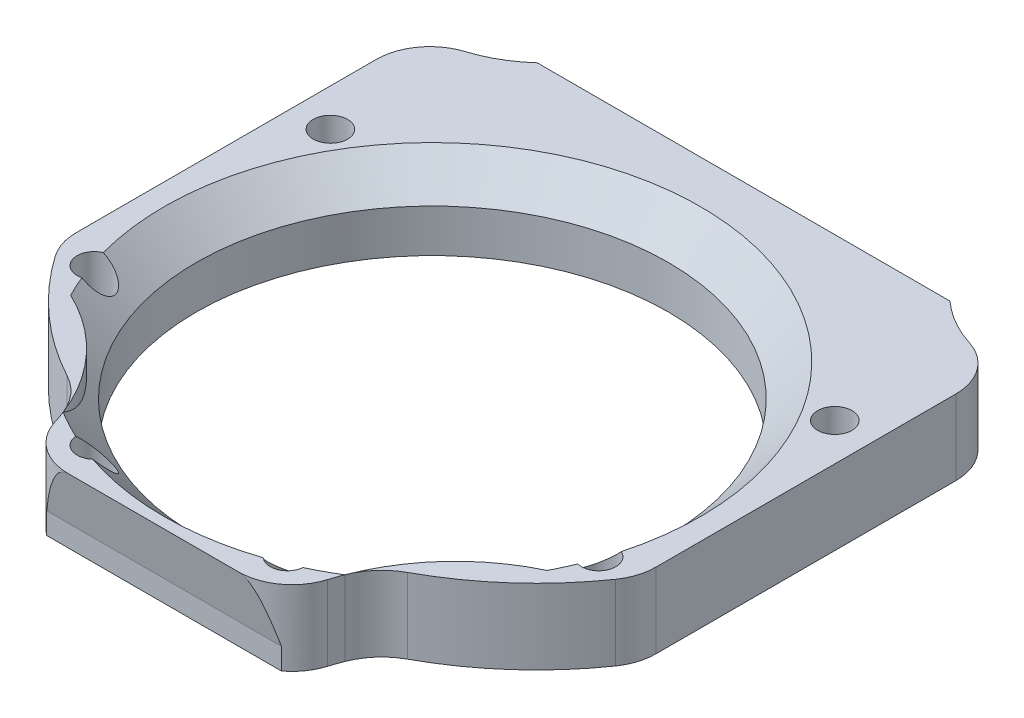
SolidWorks part; units mm, degrees
material "PBT Общее назначение"
ref_plane "Спереди" through (0, 0, 0) normal (0, 0, 1) x (1, 0, 0)
ref_plane "Сверху" through (0, 0, 0) normal (0, 1, 0) x (1, 0, 0)
ref_plane "Справа" through (0, 0, 0) normal (1, 0, 0) x (0, 0, -1)
ref_plane "Плоскость4" through (0, -5, 0) normal (0, -1, 0) x (-1, 0, 0)
sketch "Эскиз2" plane through (0, -5, 0) normal (0, -1, 0) x (-1, 0, 0)
  line L4 (-23.9302, -60) -> (-8.0698, -60)
  line L5 (-43, -12.2273) -> (-43, -40.1669)
  line L6 (3.2299, -5) -> (-35.2299, -5)
  line L7 (11, -40.1669) -> (11, -12.2273)
  line L8 (-23.9302, -60) -> (-8.0698, -60)
  line L9 (-43, -12.2273) -> (-43, -40.1669)
  line L10 (3.2299, -5) -> (-35.2299, -5)
  line L11 (11, -40.1669) -> (11, -12.2273)
  arc A10 (7.7203, -44.8616) -> (11, -40.1669) centre (6, -40.1669) ccw
  arc A11 (7.7203, -44.8616) -> (-3.2909, -56.4701) centre (13.9135, -61.7626) ccw
  arc A12 (-8.0698, -60) -> (-3.2909, -56.4701) centre (-8.0698, -55) ccw
  arc A13 (-28.7091, -56.4701) -> (-23.9302, -60) centre (-23.9302, -55) ccw
  arc A14 (-28.7091, -56.4701) -> (-39.7203, -44.8616) centre (-45.9135, -61.7626) ccw
  arc A15 (-43, -40.1669) -> (-39.7203, -44.8616) centre (-38, -40.1669) ccw
  arc A16 (-39.5094, -7.4605) -> (-43, -12.2273) centre (-38, -12.2273) ccw
  arc A17 (-39.5094, -7.4605) -> (-35.2299, -5) centre (-43, 3.5625) ccw
  arc A18 (3.2299, -5) -> (7.5094, -7.4605) centre (11, 3.5625) ccw
  arc A19 (11, -12.2273) -> (7.5094, -7.4605) centre (6, -12.2273) ccw
  arc A20 (7.7203, -44.8616) -> (11, -40.1669) centre (6, -40.1669) ccw
  arc A21 (7.7203, -44.8616) -> (-3.2909, -56.4701) centre (13.9135, -61.7626) ccw
  arc A22 (-8.0698, -60) -> (-3.2909, -56.4701) centre (-8.0698, -55) ccw
  arc A23 (-28.7091, -56.4701) -> (-23.9302, -60) centre (-23.9302, -55) ccw
  arc A24 (-28.7091, -56.4701) -> (-39.7203, -44.8616) centre (-45.9135, -61.7626) ccw
  arc A25 (-43, -40.1669) -> (-39.7203, -44.8616) centre (-38, -40.1669) ccw
  arc A26 (-39.5094, -7.4605) -> (-43, -12.2273) centre (-38, -12.2273) ccw
  arc A27 (-39.5094, -7.4605) -> (-35.2299, -5) centre (-43, 3.5625) ccw
  arc A28 (3.2299, -5) -> (7.5094, -7.4605) centre (11, 3.5625) ccw
  arc A29 (11, -12.2273) -> (7.5094, -7.4605) centre (6, -12.2273) ccw
  dimension "D1" = 0
extrude "Бобышка-Вытянуть1" add sketch "Эскиз2" along normal blind 5
sketch "Эскиз3" plane through (0, -10, 0) normal (0, -1, 0) x (1, 0, 0)
  circle A0 centre (16, 34) radius 22 construction
  circle A1 centre (16, 34) radius 22
  dimension "D1" = 44
extrude "Вырез-Вытянуть1" cut sketch "Эскиз3" against normal through all contours A1
sketch "Эскиз4" plane through (0, -10, 0) normal (0, -1, 0) x (1, 0, 0)
  circle A0 centre (39.5, 20) radius 1.6 construction
  circle A1 centre (-7.5, 20) radius 1.6 construction
  circle A2 centre (-7.5, 42) radius 1.6 construction
  circle A3 centre (39.5, 42) radius 1.6 construction
  circle A4 centre (39.5, 20) radius 1.6
  circle A5 centre (-7.5, 20) radius 1.6
  circle A6 centre (-7.5, 42) radius 1.6
  circle A7 centre (39.5, 42) radius 1.6
  circle A9 centre (25, 56.5) radius 1.6 construction
  circle A10 centre (7, 56.5) radius 1.6 construction
  circle A11 centre (25, 56.5) radius 1.6
  circle A12 centre (7, 56.5) radius 1.6
extrude "Вырез-Вытянуть3" cut sketch "Эскиз4" against normal through all
sketch "Эскиз8" plane through (43, 0, 0) normal (1, 0, 0) x (0, 0, -1)
  line L0 (-60, -10) -> (-60, -5) construction
  line L1 (-60, -10) -> (-60, -5)
  line L2 (-60, -5) -> (-59, -10)
  line L3 (-60, -10) -> (-59, -10)
  line L4 (-60, -10) -> (-60, -5) construction
  dimension "D1" = 1
  dimension "D2" = 5
extrude "Вырез-Вытянуть6" cut sketch "Эскиз8" against normal through all
sketch "Эскиз9" plane through (0, -10, 0) normal (0, -1, 0) x (1, 0, 0)
  line L4 (26.9302, 59) -> (5.0698, 59)
  line L5 (-11, 40.1669) -> (-11, 12.2273)
  line L6 (-3.2299, 5) -> (35.2299, 5)
  line L7 (43, 12.2273) -> (43, 40.1669)
  line L8 (26.9302, 59) -> (5.0698, 59)
  line L9 (-11, 40.1669) -> (-11, 12.2273)
  line L10 (-3.2299, 5) -> (35.2299, 5)
  line L11 (43, 12.2273) -> (43, 40.1669)
  circle A0 centre (39.5, 42) radius 1.6 construction
  circle A1 centre (25, 56.5) radius 1.6 construction
  circle A2 centre (39.5, 20) radius 1.6 construction
  circle A3 centre (-7.5, 20) radius 1.6 construction
  circle A4 centre (-7.5, 42) radius 1.6 construction
  circle A5 centre (7, 56.5) radius 1.6 construction
  circle A6 centre (16, 34) radius 22 construction
  circle A7 centre (39.5, 42) radius 1.6
  circle A8 centre (25, 56.5) radius 1.6
  circle A9 centre (39.5, 20) radius 1.6
  arc A10 (5.0698, 59) -> (3.2909, 56.4701) centre (8.0698, 55) ccw
  arc A11 (-7.7203, 44.8616) -> (3.2909, 56.4701) centre (-13.9135, 61.7626) ccw
  arc A12 (-7.7203, 44.8616) -> (-11, 40.1669) centre (-6, 40.1669) ccw
  arc A13 (-11, 12.2273) -> (-7.5094, 7.4605) centre (-6, 12.2273) ccw
  arc A14 (-3.2299, 5) -> (-7.5094, 7.4605) centre (-11, -3.5625) ccw
  arc A15 (39.5094, 7.4605) -> (35.2299, 5) centre (43, -3.5625) ccw
  arc A16 (39.5094, 7.4605) -> (43, 12.2273) centre (38, 12.2273) ccw
  arc A17 (43, 40.1669) -> (39.7203, 44.8616) centre (38, 40.1669) ccw
  arc A18 (28.7091, 56.4701) -> (39.7203, 44.8616) centre (45.9135, 61.7626) ccw
  arc A19 (28.7091, 56.4701) -> (26.9302, 59) centre (23.9302, 55) ccw
  arc A20 (5.0698, 59) -> (3.2909, 56.4701) centre (8.0698, 55) ccw
  arc A21 (-7.7203, 44.8616) -> (3.2909, 56.4701) centre (-13.9135, 61.7626) ccw
  arc A22 (-7.7203, 44.8616) -> (-11, 40.1669) centre (-6, 40.1669) ccw
  arc A23 (-11, 12.2273) -> (-7.5094, 7.4605) centre (-6, 12.2273) ccw
  arc A24 (-3.2299, 5) -> (-7.5094, 7.4605) centre (-11, -3.5625) ccw
  arc A25 (39.5094, 7.4605) -> (35.2299, 5) centre (43, -3.5625) ccw
  arc A26 (39.5094, 7.4605) -> (43, 12.2273) centre (38, 12.2273) ccw
  arc A27 (43, 40.1669) -> (39.7203, 44.8616) centre (38, 40.1669) ccw
  arc A28 (28.7091, 56.4701) -> (39.7203, 44.8616) centre (45.9135, 61.7626) ccw
  arc A29 (28.7091, 56.4701) -> (26.9302, 59) centre (23.9302, 55) ccw
  circle A30 centre (-7.5, 20) radius 1.6
  circle A31 centre (-7.5, 42) radius 1.6
  circle A32 centre (7, 56.5) radius 1.6
  circle A33 centre (16, 34) radius 22
  dimension "D1" = 0
extrude "Бобышка-Вытянуть2" add sketch "Эскиз9" along normal blind 2
sketch "Эскиз10" plane through (0, -12, 0) normal (0, -1, 0) x (1, 0, 0)
  line L0 (26.9302, 59) -> (5.0698, 59) construction
  arc A0 (30.1904, 53) -> (42.0989, 43.0303) centre (17.704, 25.9884) cw
  arc A1 (28.7091, 56.4701) -> (39.7203, 44.8616) centre (45.9135, 61.7626) ccw construction
  arc A2 (43, 40.1669) -> (39.7203, 44.8616) centre (38, 40.1669) ccw construction
  arc A3 (30.1904, 53) -> (39.7203, 44.8616) centre (45.9135, 61.7626) ccw
  arc A4 (42.0989, 43.0303) -> (39.7203, 44.8616) centre (38, 40.1669) ccw
  dimension "D1" = 6
extrude "Бобышка-Вытянуть3" add sketch "Эскиз10" against normal up to surface (7 mm away) up to face at (7, -5, 54.9)
sketch "Эскиз11" plane through (0, -12, 0) normal (0, -1, 0) x (1, 0, 0)
  line L0 (16, 5) -> (16, 59) construction
  line L1 (-3.2299, 5) -> (35.2299, 5) construction
  line L2 (26.9302, 59) -> (5.0698, 59) construction
ref_plane "sym" through (16, 0, 0) normal (1, 0, 0) x (0, 0, 1)
mirror "Зеркальное отражение1" about plane through (16, 0, 0) normal (1, 0, 0) of "Бобышка-Вытянуть3"
chamfer "Фаска1" distance 3 angle 45 1 edges at (16, -5, 12)
fillet "Скругление1" radius 6 2 edges at (1.8096, -9.1429, 53) (30.1904, -9.1429, 53)
sketch "Эскиз13" plane through (0, -5, 0) normal (0, 1, 0) x (1, 0, 0)
  arc A0 (39.7203, -44.8616) -> (28.7091, -56.4701) centre (45.9135, -61.7626) ccw construction
  arc A1 (41.0591, -44.4296) -> (29.1229, -55.2761) centre (45.9135, -61.7626) ccw
  arc A2 (35.0965, -50.1346) -> (42.0989, -43.0303) centre (17.704, -25.9884) ccw construction
  arc A3 (31.8646, -52.1612) -> (35.0965, -50.1346) centre (17.704, -25.9884) ccw construction
  arc A4 (31.8646, -52.1612) -> (29.1229, -55.2761) centre (34.7197, -57.4383) ccw construction
  arc A5 (35.0965, -50.1346) -> (41.0591, -44.4296) centre (17.704, -25.9884) ccw
  arc A6 (31.8646, -52.1612) -> (35.0965, -50.1346) centre (17.704, -25.9884) ccw
  arc A7 (31.8646, -52.1612) -> (29.1229, -55.2761) centre (34.7197, -57.4383) ccw
extrude "Бобышка-Вытянуть4" add sketch "Эскиз13" against normal up to surface (0.0023 mm away) up to face at (16, -8, 12)
mirror "Зеркальное отражение2" about plane through (16, 0, 0) normal (1, 0, 0) of "Бобышка-Вытянуть4"
